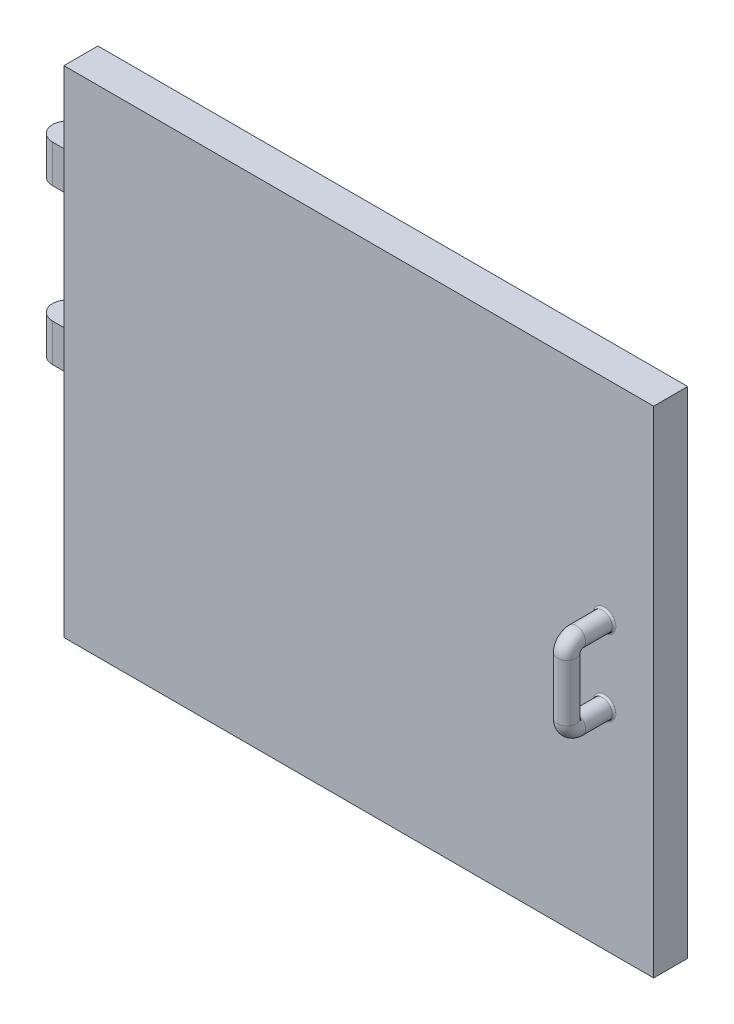
SolidWorks part; units mm, degrees
ref_plane "Alzado" through (0, 0, 0) normal (0, 0, 1) x (1, 0, 0)
ref_plane "Planta" through (0, 0, 0) normal (0, 1, 0) x (1, 0, 0)
ref_plane "Vista lateral" through (0, 0, 0) normal (1, 0, 0) x (0, 0, -1)
sketch "Croquis2" plane through (0, 0, 0) normal (0, 0, 1) x (1, 0, 0)
  line L1 (156, 131) -> (-156, 131)
  line L2 (156, 131) -> (156, -131)
  line L3 (156, -131) -> (-156, -131)
  line L4 (-156, 131) -> (-156, -131)
  line L5 (156, 131) -> (-156, -131) construction
  line L6 (156, -131) -> (-156, 131) construction
  point P0 (0, 0)
  dimension "D1" = 262
  dimension "D2" = 312
extrude "Saliente-Extruir1" add sketch "Croquis2" along normal blind 8
sketch "Croquis3" plane through (0, 0, 0) normal (0, 0, -1) x (-1, 0, 0)
  line L1 (153, -128) -> (-153, -128)
  line L2 (153, -128) -> (153, 128)
  line L3 (153, 128) -> (-153, 128)
  line L4 (-153, -128) -> (-153, 128)
  line L5 (153, -128) -> (-153, 128) construction
  line L6 (153, 128) -> (-153, -128) construction
  line L7 (156, -131) -> (-156, -131)
  line L8 (156, -131) -> (156, 131)
  line L9 (156, 131) -> (-156, 131)
  line L10 (-156, -131) -> (-156, 131)
  line L11 (156, -131) -> (-156, 131) construction
  line L12 (156, 131) -> (-156, -131) construction
  point P0 (0, 0)
  point P6 (0, 0)
  dimension "D1" = 306
  dimension "D2" = 256
extrude "Saliente-Extruir2" add sketch "Croquis3" along normal blind 10
sketch "Croquis6" plane through (-156, 0, 0) normal (-1, 0, 0) x (0, 0, 1)
  line L0 (8, 131) -> (-10, 131) construction
  line L1 (-10, 91) -> (6, 91)
  line L2 (-10, 91) -> (-10, 71)
  line L3 (-10, 71) -> (6, 71)
  line L4 (6, 91) -> (6, 71)
  line L5 (-10, 91) -> (6, 71) construction
  line L6 (-10, 71) -> (6, 91) construction
  line L7 (-10, 9) -> (6, 9)
  line L8 (-10, 9) -> (-10, -11)
  line L9 (-10, -11) -> (6, -11)
  line L10 (6, 9) -> (6, -11)
  line L11 (-10, 9) -> (6, -11) construction
  line L12 (-10, -11) -> (6, 9) construction
  line L13 (8, -131) -> (-10, -131) construction
  line L14 (-10, -131) -> (-10, 131) construction
  point P0 (-2, 81)
  point P5 (-2, -1)
  dimension "D1" = 40
  dimension "D2" = 120
  dimension "D3" = 20
  dimension "D4" = 20
  dimension "D5" = 16
  dimension "D6" = 16
extrude "Saliente-Extruir6" add sketch "Croquis6" along normal blind 8
sketch "Croquis7" plane through (0, 91, 0) normal (0, 1, 0) x (1, 0, 0)
  line L0 (-164, 10) -> (-164, -6)
  arc A0 (-164, 10) -> (-164, -6) centre (-164, 2) ccw
extrude "Saliente-Extruir7" add sketch "Croquis7" against normal blind 20
sketch "Croquis8" plane through (0, 9, 0) normal (0, 1, 0) x (1, 0, 0)
  line L0 (-164, -6) -> (-164, 10) construction
  line L1 (-164, 10) -> (-164, -6)
  arc A0 (-164, 10) -> (-164, -6) centre (-164, 2) ccw
extrude "Saliente-Extruir8" add sketch "Croquis8" against normal blind 20
sketch "Croquis9" plane through (0, 71, 0) normal (0, -1, 0) x (1, 0, 0)
  circle A0 centre (-164, -2) radius 3.5
  arc A1 (-164, 6) -> (-164, -10) centre (-164, -2) ccw construction
  dimension "D1" = 7
extrude "Cortar-Extruir1" cut sketch "Croquis9" against normal blind 5
sketch "Croquis10" plane through (0, -11, 0) normal (0, -1, 0) x (1, 0, 0)
  circle A0 centre (-164, -2) radius 3.5
  arc A1 (-164, 6) -> (-164, -10) centre (-164, -2) ccw construction
  dimension "D1" = 7
extrude "Cortar-Extruir2" cut sketch "Croquis10" against normal blind 5
sketch "Croquis11" plane through (0, 0, 8) normal (0, 0, 1) x (1, 0, 0)
  line L0 (0, 0) -> (130, 0) construction
  circle A0 centre (130, 20) radius 5
  circle A2 centre (130, -20) radius 5
  dimension "D4" = 10
  dimension "D3" = 10
  dimension "D1" = 20
  dimension "D2" = 20
ref_plane "Plano1" through (130, 0, 0) normal (1, 0, 0) x (0, 0, -1)
sketch "Croquis13" plane through (130, 0, 0) normal (1, 0, 0) x (0, 0, -1)
  line L0 (-8, 20) -> (-23, 20)
  line L1 (-8, 25) -> (-8, 15) construction
  line L2 (-28, 15) -> (-28, -15)
  line L5 (-8, -131) -> (-8, 131) construction
  line L6 (-8, -20) -> (-23, -20)
  arc A0 (-23, 20) -> (-28, 15) centre (-23, 15) ccw
  arc A2 (-28, -15) -> (-23, -20) centre (-23, -15) ccw
  dimension "D2" = 10
  dimension "D5" = 10
  dimension "D1" = 15
  dimension "D4" = 15
sweep "Barrer7" add path "Croquis13" circular profile diameter 10 parameters "D3"=10
fillet "Redondeo1" radius 1 2 edges at (135, -20, 8) (135, 20, 8)
